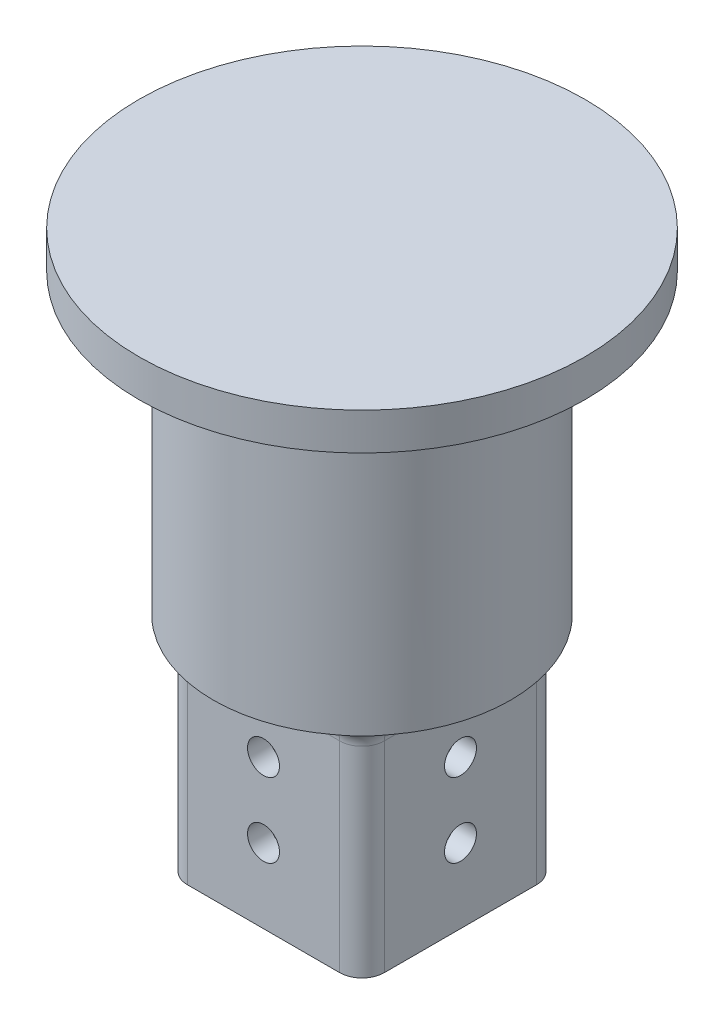
SolidWorks part; units mm, degrees
ref_plane "前视基准面" through (0, 0, 0) normal (0, 0, 1) x (1, 0, 0)
ref_plane "上视基准面" through (0, 0, 0) normal (0, 1, 0) x (1, 0, 0)
ref_plane "右视基准面" through (0, 0, 0) normal (1, 0, 0) x (0, 0, -1)
other "Configuration Table"
sketch "草图1" plane through (0, 0, 0) normal (0, 1, 0) x (1, 0, 0)
  line L1 (-10.25, -10.25) -> (10.25, -10.25)
  line L2 (-10.25, -10.25) -> (-10.25, 10.25)
  line L3 (-10.25, 10.25) -> (10.25, 10.25)
  line L4 (10.25, -10.25) -> (10.25, 10.25)
  line L5 (-10.25, -10.25) -> (10.25, 10.25) construction
  line L6 (-10.25, 10.25) -> (10.25, -10.25) construction
  circle A0 centre (0, 0) radius 20
  dimension "D1" = 40
  dimension "D2" = 20.5
  dimension "D3" = 20.5
extrude "凸台-拉伸1" add sketch "草图1" along normal blind 30
sketch "草图3" plane through (0, 0, 0) normal (0, -1, 0) x (1, 0, 0)
  line L11 (-10.25, 10.25) -> (10.25, 10.25)
  line L12 (-10.25, 10.25) -> (-10.25, -10.25)
  line L13 (-10.25, -10.25) -> (10.25, -10.25)
  line L14 (13.25, -13.25) -> (13.25, 13.25)
  line L15 (-13.25, -13.25) -> (13.25, -13.25)
  line L16 (-13.25, 13.25) -> (-13.25, -13.25)
  line L17 (13.25, 13.25) -> (-13.25, 13.25)
  line L18 (13.25, -13.25) -> (13.25, 13.25)
  line L19 (-13.25, -13.25) -> (13.25, -13.25)
  line L20 (-13.25, 13.25) -> (-13.25, -13.25)
  line L21 (13.25, 13.25) -> (-13.25, 13.25)
  line L22 (10.25, 10.25) -> (10.25, -10.25)
  dimension "D1" = 3
sketch "草图5" plane through (0, 30, 0) normal (0, 1, 0) x (1, 0, 0)
  circle A0 centre (0, 0) radius 20
extrude "凸台-拉伸3" add sketch "草图5" along normal blind 10
extrude "凸台-拉伸4" add sketch "草图3" along normal blind 30
sketch "草图6" plane through (0, 0, 13.25) normal (0, 0, 1) x (1, 0, 0)
  line L0 (0, 0) -> (0, -10)
  line L1 (0, -10) -> (0, -20)
  circle A0 centre (0, -10) radius 2.15
  circle A1 centre (0, -20) radius 2.15
  dimension "D2" = 4.3
  dimension "D4" = 4.3
  dimension "D1" = 10
  dimension "D3" = 10
extrude "切除-拉伸1" cut sketch "草图6" against normal blind 30 contours A0 | A1
sketch "草图7" plane through (-13.25, 0, 0) normal (-1, 0, 0) x (0, 0, 1)
  line L0 (0, -1000) -> (0, 49000) construction
  circle A0 centre (0, -10) radius 2.15
  circle A1 centre (0, -20) radius 2.15
  dimension "D3" = 4.3
  dimension "D4" = 4.3
  dimension "D1" = 10
  dimension "D2" = 10
extrude "切除-拉伸2" cut sketch "草图7" against normal blind 30
fillet "圆角1" radius 3 1 edges at (-13.25, -15, 13.25) type face fillet first side face at (-13.25, -10, 2.15) second side face at (2.15, -10, 13.25)
fillet "圆角2" radius 3 1 edges at (13.25, -15, 13.25) type face fillet first side face at (2.15, -10, 13.25) second side face at (13.25, -10, 2.15)
fillet "圆角3" radius 3 1 edges at (13.25, -15, -13.25) type face fillet first side face at (13.25, -10, 2.15) second side face at (2.15, -10, -13.25)
fillet "圆角4" radius 3 1 edges at (-13.25, -15, -13.25) type face fillet first side face at (2.15, -10, -13.25) second side face at (-13.25, -10, 2.15)
fillet "圆角5" radius 3 8 edges at (-12.3713, 0, -12.3713) (12.3713, 0, -12.3713) (12.3713, 0, 12.3713) (-12.3713, 0, 12.3713) (0, 0, -13.25) (-13.25, 0, 0) (0, 0, 13.25) (13.25, 0, 0) type face fillet first side face at (12.0607, -15, 12.0607) first side face at (-12.0607, -15, 12.0607) first side face at (-12.0607, -15, -12.0607) first side face at (12.0607, -15, -12.0607) first side face at (13.25, -10, 2.15) first side face at (2.15, -10, -13.25) first side face at (-13.25, -10, 2.15) first side face at (2.15, -10, 13.25) second side face at (0, 0, 20)
sketch "草图11" plane through (0, 40, 0) normal (0, 1, 0) x (1, 0, 0)
  circle A0 centre (0, 0) radius 30
  dimension "D1" = 60
extrude "凸台-拉伸5" add sketch "草图11" along normal blind 5
fillet "圆角6" radius 5 1 edges at (0, 40, 20) type face fillet first side face at (0, 40, 20) second side face at (0, 0, 0)
